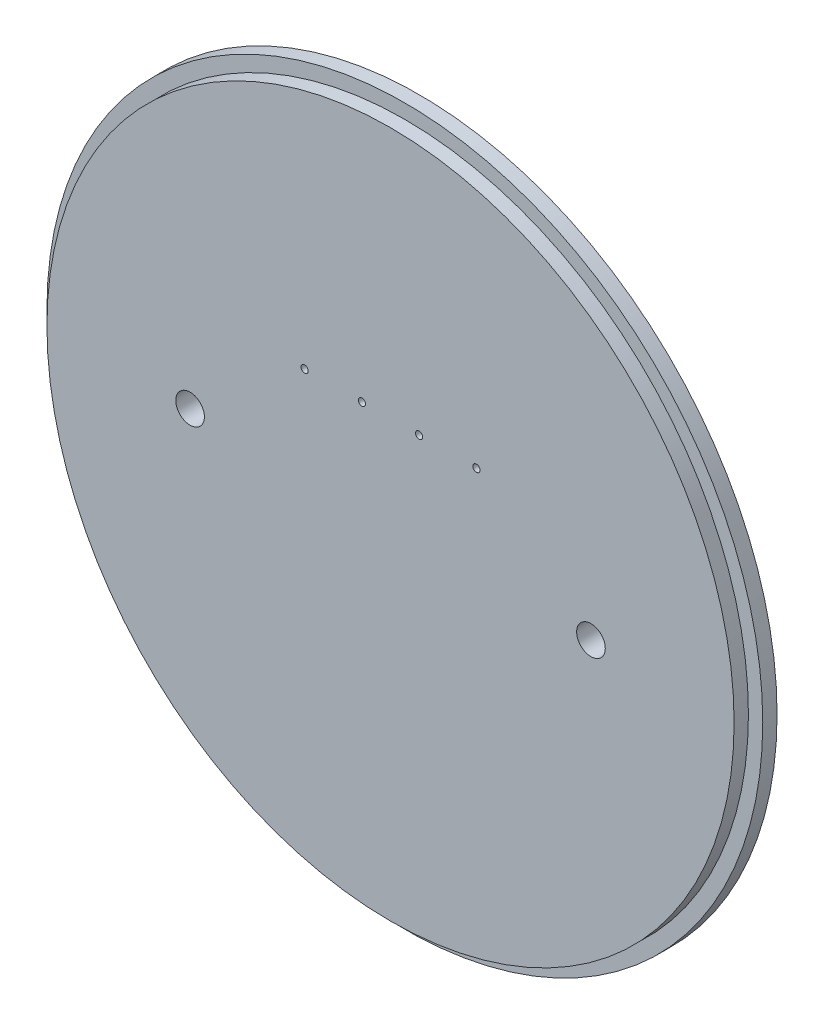
SolidWorks part; units mm, degrees
ref_plane "Front Plane" through (0, 0, 0) normal (0, 0, 1) x (1, 0, 0)
ref_plane "Top Plane" through (0, 0, 0) normal (0, 1, 0) x (1, 0, 0)
ref_plane "Right Plane" through (0, 0, 0) normal (1, 0, 0) x (0, 0, -1)
sketch "Sketch1" plane through (0, 0, 0) normal (0, 0, 1) x (1, 0, 0)
  circle A0 centre (0, 0) radius 79.375
  dimension "D1" = 158.75
extrude "Boss-Extrude1" add sketch "Sketch1" along normal blind 3.175
sketch "Sketch2" plane through (0, 0, 3.175) normal (0, 0, 1) x (1, 0, 0)
  circle A0 centre (0, 0) radius 76.2
  dimension "D1" = 152.4
extrude "Boss-Extrude2" add sketch "Sketch2" along normal blind 3.175
sketch "Sketch4" plane through (0, 0, 6.35) normal (0, 0, 1) x (1, 0, 0)
  line L0 (0, 0) -> (44.45, 0) construction
  line L1 (0, 0) -> (-44.45, 0) construction
  point P1 (-44.45, 0)
  point P3 (44.45, 0)
  dimension "D1" = 88.9
hole_wizard "1/4 (0.25) Diameter Hole1" positions "Sketch7" profile "Sketch9" hole size "1/4" standard "ANSI Inch" end condition through all
sketch "Sketch7" plane through (0, 0, 6.35) normal (0, 0, 1) x (1, 0, 0)
  point P0 (-44.45, 0)
  point P3 (44.45, 0)
sketch "Sketch9" plane through (-44.45, 0, 6.35) normal (1, 0, 0) x (0, -1, 0)
  line L0 (0, 0) -> (0, 6.35)
  line L1 (0, 6.35) -> (3.175, 6.35)
  line L2 (3.175, 6.35) -> (3.175, 0)
  line L5 (3.175, 0) -> (0, 0)
  line L11 (0, -6.35) -> (0, 107.95) construction
  dimension "Thru Hole Dia." = 6.35
  dimension "Thru Hole Depth" = 6.35
sketch "Sketch11" plane through (0, 0, 6.35) normal (0, 0, 1) x (1, 0, 0)
  line L0 (-19.05, 20.32) -> (19.05, 20.32) construction
  point P2 (0, 20.32)
  point P3 (0, 0)
  point P5 (-19.05, 20.32)
  point P6 (19.05, 20.32)
  point P7 (-6.35, 20.32)
  point P8 (6.35, 20.32)
  point P9 (19.05, 20.32)
  point P10 (19.05, 20.32)
  dimension "D1" = 38.1
  dimension "D2" = 20.32
  dimension "D3" = 4
hole_wizard "1/16 (0.0625) Diameter Hole1" positions "Sketch12" profile "Sketch13" hole size "1/16" standard "ANSI Inch" end condition through all
sketch "Sketch12" plane through (0, 0, 6.35) normal (0, 0, 1) x (1, 0, 0)
  point P0 (-19.05, 20.32)
  point P3 (-6.35, 20.32)
  point P6 (6.35, 20.32)
  point P9 (19.05, 20.32)
sketch "Sketch13" plane through (-19.05, 20.32, 6.35) normal (1, 0, 0) x (0, -1, 0)
  line L0 (0, 0) -> (0, 6.35)
  line L1 (0, 6.35) -> (0.7937, 6.35)
  line L2 (0.7937, 6.35) -> (0.7937, 0)
  line L5 (0.7937, 0) -> (0, 0)
  line L11 (0, -6.35) -> (0, 107.95) construction
  dimension "Thru Hole Dia." = 1.5875
  dimension "Thru Hole Depth" = 6.35
